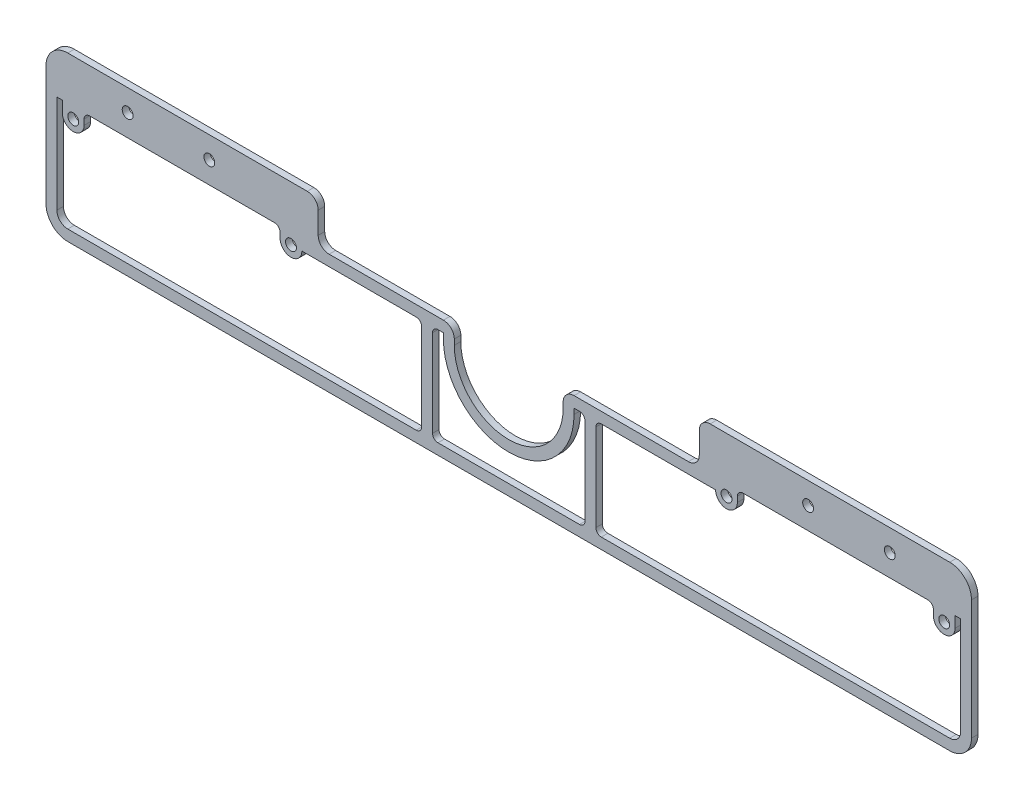
SolidWorks part; units mm, degrees
ref_plane "Front Plane" through (0, 0, 0) normal (0, 0, 1) x (1, 0, 0)
ref_plane "Top Plane" through (0, 0, 0) normal (0, 1, 0) x (1, 0, 0)
ref_plane "Right Plane" through (0, 0, 0) normal (1, 0, 0) x (0, 0, -1)
sketch "Sketch1" plane through (0, 0, 0) normal (0, 0, 1) x (1, 0, 0)
  line L0 (-50, 0) -> (-50, 35) construction
  line L1 (405, -95) -> (-405, -95) construction
  line L4 (-425, -75) -> (-425, 35)
  line L8 (-60, 55) -> (-405, 55) construction
  line L21 (-165.0003, 15) -> (-60, 15)
  line L25 (0, -50) -> (0, -95)
  line L26 (0, 55) -> (0, -95) construction
  line L27 (-50, 75) -> (50, 75) construction
  line L32 (-50, 5) -> (-50, 0)
  line L34 (0, -95) -> (-405, -95)
  line L170 (-405, 55) -> (-185.0003, 55)
  line L175 (-175.0003, 45) -> (-175.0003, 25)
  circle A1 centre (0, 0) radius 30 construction
  arc A4 (-405, -95) -> (-425, -75) centre (-405, -75) cw
  arc A5 (-425, 35) -> (-405, 55) centre (-405, 35) cw
  circle A26 centre (-350, 35) radius 5
  circle A27 centre (-275, 35) radius 5
  arc A136 (-50, 0) -> (0, -50) centre (0, 0) ccw
  arc A137 (-50, 5) -> (-60, 15) centre (-60, 5) ccw
  arc A138 (-165.0003, 15) -> (-175.0003, 25) centre (-165.0003, 25) cw
  arc A139 (-175.0003, 45) -> (-185.0003, 55) centre (-185.0003, 45) ccw
  point P1 (0, 0)
  point P2 (0, 0)
  point P3 (0, 0)
  point P4 (0, 0)
  point P10 (0, -21.413)
  point P11 (0, 30)
  point P15 (-50, 15)
  point P27 (-175.0003, 55)
  point P30 (-50, 55)
  point P32 (0, 0)
  point P33 (0, 0)
  point P34 (0, 0)
  point P74 (0, 75)
  dimension "D3" = 10
  dimension "D4" = 60
  dimension "D6" = 55
  dimension "D7" = 425
  dimension "D10" = 175.0003
  dimension "D11" = 20
  dimension "D12" = 50
  dimension "D20" = 10
  dimension "D21" = 10
  dimension "D5" = 150
  dimension "D9" = 40
  dimension "D16" = 100
  dimension "D17" = 20
  dimension "D18" = 375
  dimension "D19" = 20
  dimension "D22" = 20
  dimension "D23" = 75
  dimension "D24" = 225
  dimension "D8" = 345
extrude "Boss-Extrude1" add sketch "Sketch1" along normal blind 6
mirror "Mirror1" about plane through (0, -50, 6) normal (-1, 0, 0) of "Boss-Extrude1"
sketch "Sketch2" plane through (0, 0, 6) normal (0, 0, 1) x (1, 0, 0)
  line L0 (0, -29.253) -> (0, -89.121) construction
  line L2 (-185.0003, 55) -> (-405, 55) construction
  line L49 (-410, 5) -> (-410, 15)
  line L50 (-410, 15) -> (-415, 15)
  line L51 (-390, 5) -> (-390, 10)
  line L52 (-385, 15) -> (-215, 15)
  line L53 (-210, 10) -> (-210, 5)
  line L54 (-190, 5) -> (-165.0003, 5)
  line L55 (-185.0003, 45) -> (-405, 45)
  line L56 (-185.0003, 25) -> (-185.0003, 45)
  line L57 (-60, 0) -> (-60, 5)
  line L58 (-60, 5) -> (-165.0003, 5)
  line L59 (-415, 35) -> (-415, -75)
  line L60 (-405, -85) -> (405, -85)
  line L61 (-185.0003, 45) -> (-405, 45) construction
  line L62 (-185.0003, 25) -> (-185.0003, 45) construction
  line L63 (-60, 0) -> (-60, 5)
  line L64 (-85, 5) -> (-165.0003, 5)
  line L65 (-415, 35) -> (-415, -75) construction
  line L66 (-405, -85) -> (-85, -85)
  line L67 (0, -60) -> (0, -85)
  line L68 (-415, 15) -> (-415, -75)
  line L69 (-80, 0) -> (-80, -80)
  line L70 (-70, 0) -> (-70, -80)
  line L71 (-65, 5) -> (-60, 5)
  line L72 (-65, -85) -> (0, -85)
  circle A0 centre (-400, 5) radius 5
  circle A1 centre (-200, 5) radius 5
  arc A2 (-410, 5) -> (-390, 5) centre (-400, 5) ccw
  arc A3 (-210, 5) -> (-190, 5) centre (-200, 5) ccw
  arc A4 (-65, -85) -> (-70, -80) centre (-65, -80) cw
  arc A5 (-70, 0) -> (-65, 5) centre (-65, 0) cw
  arc A43 (-80, 0) -> (-85, 5) centre (-85, 0) ccw
  arc A44 (-85, -85) -> (-80, -80) centre (-85, -80) ccw
  arc A45 (-385, 15) -> (-390, 10) centre (-385, 10) ccw
  arc A46 (-210, 10) -> (-215, 15) centre (-215, 10) ccw
  arc A49 (-405, 45) -> (-415, 35) centre (-405, 35) ccw
  arc A50 (-185.0003, 25) -> (-165.0003, 5) centre (-165.0003, 25) ccw
  arc A51 (-60, 0) -> (60, 0) centre (0, 0) ccw
  arc A52 (-415, -75) -> (-405, -85) centre (-405, -75) ccw
  arc A53 (-405, 45) -> (-415, 35) centre (-405, 35) ccw construction
  arc A54 (-185.0003, 25) -> (-165.0003, 5) centre (-165.0003, 25) ccw construction
  arc A55 (-60, 0) -> (0, -60) centre (0, 0) ccw
  arc A56 (-415, -75) -> (-405, -85) centre (-405, -75) ccw
  point P8 (-400, 15)
  point P34 (-70, -85)
  point P37 (-70, 5)
  dimension "D1" = 10
  dimension "D3" = 20
  dimension "D9" = 5
  dimension "D10" = 5
  dimension "D11" = 5
  dimension "D12" = 5
  dimension "D2" = 40
  dimension "D4" = 400
  dimension "D5" = 200
  dimension "D7" = 20
  dimension "D8" = 10
  dimension "D6" = 10
extrude "Cut-Extrude1" cut sketch "Sketch2" against normal through all contours L68 A56 L66 L67 A55 L63 L64 L54 A3 L53 L52 L51 A2 L49 L50 | A1 | A0 | A55 L63 L71 A5 L70 A4 L72 L67 | A55 L67 L72 A4 L70 A5 L71 L63 region at (-250.1525, -37.4707, 6) region at (-43.8862, -57.0304, 6) region at (-400, 5, 6) region at (-200, 5, 6)
mirror "Mirror2" about plane through (0, 0, 0) normal (1, 0, 0) of "Cut-Extrude1"
